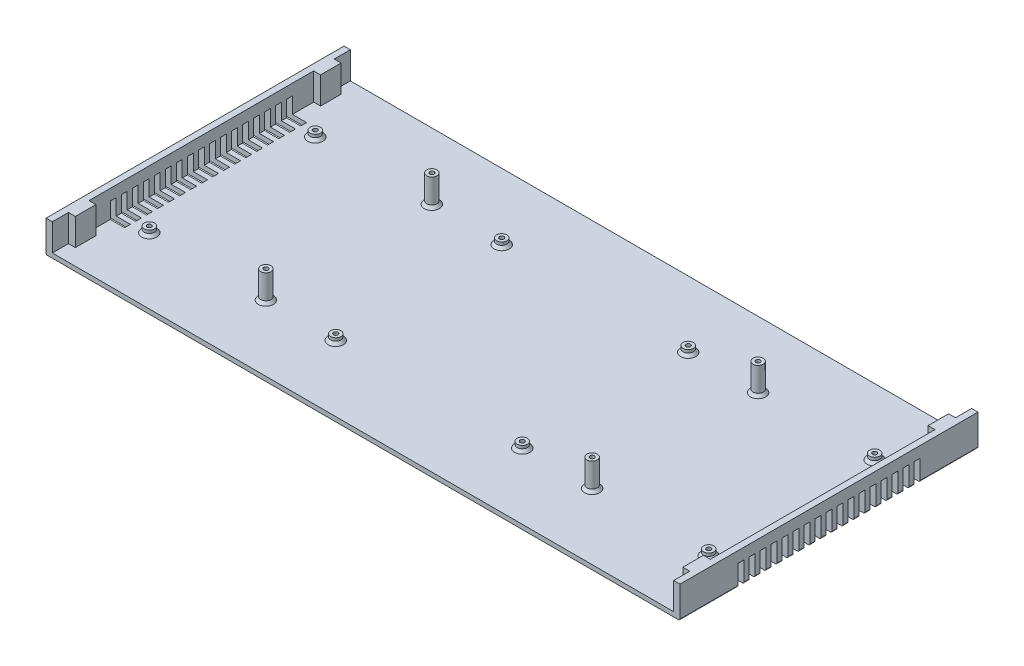
SolidWorks part; units mm, degrees
note: The reader was unsure of these and kept them because the rebuilt part matched: shared geometry of "Эскиз5<3>".
ref_plane "Спереди" through (0, 0, 0) normal (0, 0, 1) x (1, 0, 0)
ref_plane "Сверху" through (0, 0, 0) normal (0, 1, 0) x (1, 0, 0)
ref_plane "Справа" through (0, 0, 0) normal (1, 0, 0) x (0, 0, -1)
sketch "Эскиз1" plane through (0, 0, 0) normal (0, 0, 1) x (1, 0, 0)
  line L0 (-215.9, 0) -> (215.9, 0)
  line L1 (215.9, 0) -> (215.9, 21.5)
  line L2 (215.9, 21.5) -> (211.6, 21.5)
  line L3 (211.6, 21.5) -> (211.6, 3.1)
  line L4 (211.6, 3.1) -> (-211.6, 3.1)
  line L5 (-211.6, 3.1) -> (-211.6, 21.5)
  line L6 (-211.6, 21.5) -> (-215.9, 21.5)
  line L7 (-215.9, 21.5) -> (-215.9, 0)
  dimension "D1" = 431.8
  dimension "D2" = 4.3
  dimension "D3" = 3.1
  dimension "D4" = 21.5
extrude "Бобышка-Вытянуть1" add sketch "Эскиз1" along normal mid plane 203
sketch "Эскиз6" plane through (0, 0, 0) normal (0, 1, 0) x (1, 0, 0)
  line L0 (-215.9, -101.5) -> (-215.9, 101.5) construction
  line L1 (-215.9, -90.5) -> (-206.9, -90.5)
  line L2 (-215.9, -90.5) -> (-215.9, -76.5)
  line L3 (-215.9, -76.5) -> (-206.9, -76.5)
  line L4 (-206.9, -90.5) -> (-206.9, -76.5)
  line L5 (211.6, -101.5) -> (-211.6, -101.5) construction
  dimension "D1" = 11
  dimension "D2" = 9
  dimension "D3" = 14
extrude "Бобышка-Вытянуть4" add sketch "Эскиз6" along normal up to surface (21.5 mm away) up to face at (-213.75, 21.5, 0)
mirror "Зеркальное отражение5" about plane through (0, 0, 0) normal (0, 0, 1) of "Бобышка-Вытянуть4"
mirror "Зеркальное отражение6" about plane through (0, 0, 0) normal (1, 0, 0) of "Зеркальное отражение5", "Бобышка-Вытянуть4"
fillet "Скругление1" radius 1 2 edges at (215.9, 0, 0) (-215.9, 0, 0)
sketch "Эскиз2" plane through (0, 0, 0) normal (0, 1, 0) x (1, 0, 0)
  line L0 (-215.9, -101.5) -> (-215.9, 101.5) construction
  line L1 (-215.9, -2) -> (-201.9, -2)
  line L2 (-215.9, -2) -> (-215.9, 2)
  line L3 (-215.9, 2) -> (-201.9, 2)
  line L4 (-201.9, -2) -> (-201.9, 2)
  point P6 (-201.9, 0)
  dimension "D1" = 14
  dimension "D2" = 4
extrude "Вырез-Вытянуть2" cut sketch "Эскиз2" along normal blind 14
pattern_linear "Линейный массив1" count 9 spacing 7.5 along (0, 0, 1) of "Вырез-Вытянуть2"
mirror "Зеркальное отражение1" about plane through (0, 0, 0) normal (0, 0, 1) of "Линейный массив1"
mirror "Зеркальное отражение2" about plane through (0, 0, 0) normal (1, 0, 0) of "Зеркальное отражение1", "Линейный массив1"
sketch "Эскиз3" plane through (0, 0, 0) normal (0, 1, 0) x (1, 0, 0)
  point P0 (-63.5, -56.5159)
  point P1 (-111.1, -56.5159)
  point P2 (-190.5, -56.5159)
  dimension "D1" = 111.1
  dimension "D2" = 190.5
  dimension "D3" = 127
sketch "Эскиз5" plane through (0, 0, 0) normal (0, 1, 0) x (1, 0, 0)
  circle A2 centre (-190.5, -56.5159) radius 3.5
  circle A3 centre (-190.5, -56.5159) radius 1.5
  circle A6 centre (-111.1, -56.5159) radius 3.5
  circle A7 centre (-111.1, -56.5159) radius 1.5
  circle A8 centre (-63.5, -56.5159) radius 3.5
  circle A9 centre (-63.5, -56.5159) radius 1.5
  dimension "D1" = 7
  dimension "D2" = 3
extrude "Бобышка-Вытянуть2" add sketch "Эскиз5" along normal blind 4 from surface at 3.1 contours A2 A3 | A8 A9 starting at face at (0, 3.1, 0)
extrude "Бобышка-Вытянуть3" add sketch "Эскиз5<3>" along normal blind 18.5 from surface at 3.1 contours A6 A7 starting at face at (-63.5, 3.1, 53.0159)
sketch "Эскиз5<3>" plane through (0, 0, 0) normal (0, 1, 0) x (1, 0, 0) same geometry as "Эскиз5"
mirror "Зеркальное отражение3" about plane through (0, 0, 0) normal (0, 0, 1) of "Бобышка-Вытянуть3", "Бобышка-Вытянуть2"
mirror "Зеркальное отражение4" about plane through (0, 0, 0) normal (1, 0, 0) of "Зеркальное отражение3", "Бобышка-Вытянуть2", "Бобышка-Вытянуть3"
chamfer "Фаска1" distance 2 angle 40 12 edges at (111.1, 3.1, 53.0159) (111.1, 3.1, -60.0159) (-111.1, 3.1, 53.0159) (-111.1, 3.1, -60.0159) (190.5, 3.1, 53.0159) (190.5, 3.1, -60.0159) (63.5, 3.1, 53.0159) (63.5, 3.1, -60.0159) (-63.5, 3.1, 53.0159) (-63.5, 3.1, -60.0159) (-190.5, 3.1, 53.0159) (-190.5, 3.1, -60.0159)
